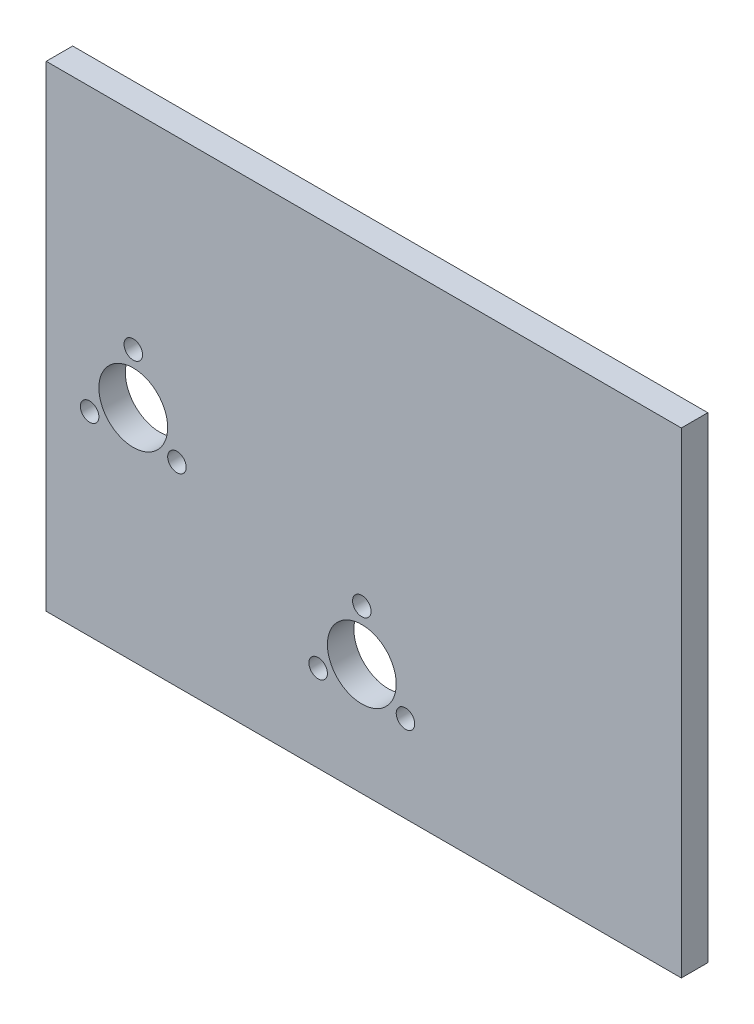
SolidWorks part; units mm, degrees
ref_plane "前视基准面" through (0, 0, 0) normal (0, 0, 1) x (1, 0, 0)
ref_plane "上视基准面" through (0, 0, 0) normal (0, 1, 0) x (1, 0, 0)
ref_plane "右视基准面" through (0, 0, 0) normal (1, 0, 0) x (0, 0, -1)
other "Configuration Table"
sketch "草图1" plane through (0, 0, 0) normal (0, 0, 1) x (1, 0, 0)
  line L1 (60, -45) -> (-60, -45)
  line L2 (60, -45) -> (60, 45)
  line L3 (60, 45) -> (-60, 45)
  line L4 (-60, -45) -> (-60, 45)
  line L5 (60, -45) -> (-60, 45) construction
  line L6 (60, 45) -> (-60, -45) construction
  point P0 (0, 0)
  dimension "D1" = 120
  dimension "D2" = 90
extrude "凸台-拉伸1" add sketch "草图1" along normal blind 5
sketch "草图2" plane through (0, 0, 0) normal (0, 0, -1) x (-1, 0, 0)
  circle A0 centre (0.3679, -23.85) radius 9.525
  circle A1 centre (43.5504, -3.4579) radius 9.525
  dimension "D1" = 19.05
  dimension "D2" = 19.05
sketch "草图3" plane through (0, 0, 0) normal (0, 0, -1) x (-1, 0, 0)
  circle A0 centre (43.5504, 6.0671) radius 1.75
  circle A1 centre (43.5504, -3.4579) radius 9.525 construction
  circle A2 centre (0.3679, -14.325) radius 1.75
  circle A3 centre (0.3679, -23.85) radius 9.525 construction
  circle A4 centre (51.7993, -8.2204) radius 1.75
  circle A5 centre (35.3015, -8.2204) radius 1.75
  circle A6 centre (8.6168, -28.6125) radius 1.75
  circle A7 centre (-7.8809, -28.6125) radius 1.75
  point P14 (43.5504, -3.4579)
  point P19 (0.3679, -23.85)
  dimension "D1" = 3.5
  dimension "D2" = 3.5
  dimension "D3" = 3
  dimension "D4" = 3
extrude "切除-拉伸1" cut sketch "草图3" against normal blind 10
sketch "草图4" plane through (0, 0, 0) normal (0, 0, -1) x (-1, 0, 0)
  circle A0 centre (0.3679, -23.85) radius 6.5
  circle A1 centre (43.5504, -3.4579) radius 6.5
  dimension "D1" = 13
  dimension "D2" = 13
extrude "切除-拉伸2" cut sketch "草图4" against normal blind 10
